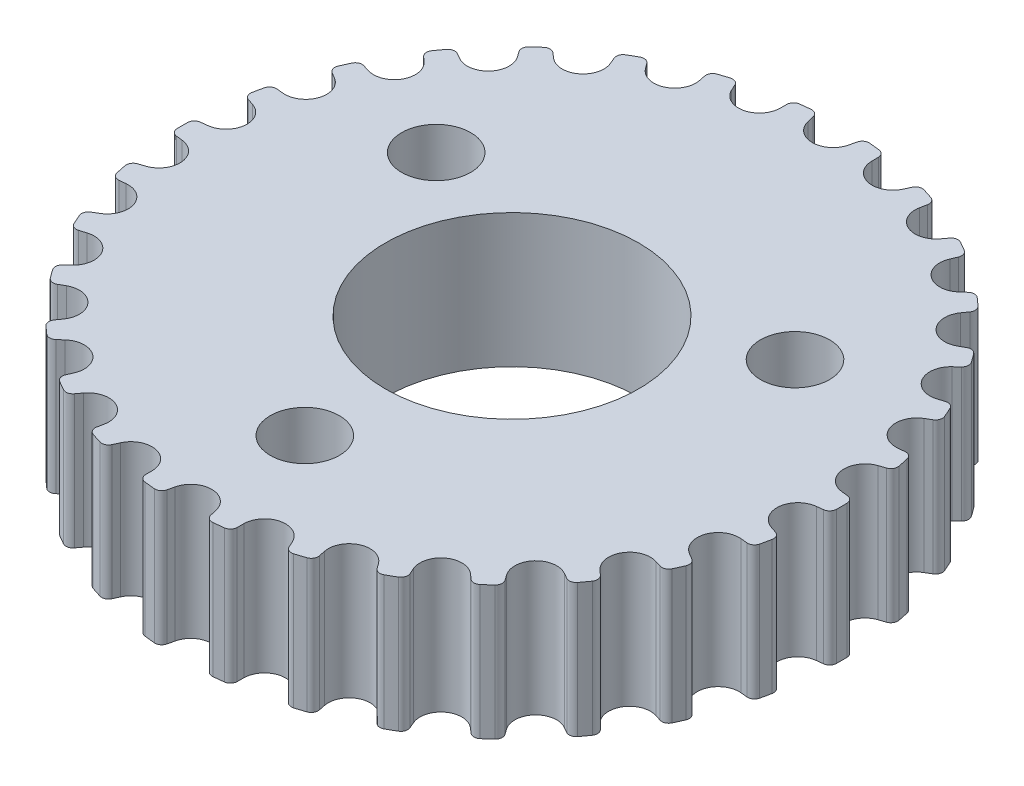
SolidWorks part; units mm, degrees
material "Acrylic (Medium-high impact)"
ref_plane "Front Plane" through (0, 0, 0) normal (0, 0, 1) x (1, 0, 0)
ref_plane "Top Plane" through (0, 0, 0) normal (0, 1, 0) x (1, 0, 0)
ref_plane "Right Plane" through (0, 0, 0) normal (1, 0, 0) x (0, 0, -1)
sketch "Sketch1" plane through (0, 0, 0) normal (0, 1, 0) x (1, 0, 0)
  circle A0 centre (0, 0) radius 14.3239
  dimension "D1" = 28.6479
extrude "Boss-Extrude1" add sketch "Sketch1" along normal blind 5.8
sketch "Sketch2" plane through (0, 5.8, 0) normal (0, 1, 0) x (1, 0, 0)
  line L0 (0, 0) -> (0, 14.3239) construction
  line L1 (-0.8883, 13.7564) -> (-0.95, 14.0339)
  line L2 (-2.9781, 14.0109) -> (-2.9781, 14.3239)
  line L3 (-2.9781, 14.3239) -> (2.9781, 14.3239)
  line L4 (0.8883, 13.7564) -> (0.95, 14.0339)
  line L5 (2.9781, 14.0109) -> (2.9781, 14.3239)
  circle A0 centre (0, 0) radius 14.3239 construction
  arc A1 (0.8883, 13.7564) -> (-0.8883, 13.7564) centre (0, 13.9539) cw
  arc A2 (-0.95, 14.0339) -> (-1.2694, 14.2676) centre (-1.2428, 13.9688) ccw
  arc A4 (0.95, 14.0339) -> (1.2694, 14.2676) centre (1.2428, 13.9688) cw
  arc A5 (-1.2694, 14.2676) -> (-2.9781, 14.0109) centre (0, 0) ccw
  arc A6 (1.2694, 14.2676) -> (2.9781, 14.0109) centre (0, 0) cw
  circle A8 centre (0, 0) radius 14.3239 construction
  point P11 (0, 14.3239)
  point P19 (0, 13.0439)
  dimension "D3" = 0.3
  dimension "D5" = 0.91
  dimension "D2" = 0.95
  dimension "D4" = 1.28
  dimension "D6" = 12
extrude "Cut-Extrude1" cut sketch "Sketch2" against normal through all
pattern_circular "CirPattern1" count 30 over 360 about axis through (0, 5.8, 0) along (0, -1, 0) of "Cut-Extrude1"
sketch "Sketch3" plane through (0, 0, 0) normal (0, -1, 0) x (1, 0, 0)
  circle A0 centre (0, 0) radius 5.5
  dimension "D1" = 11
extrude "Cut-Extrude2" cut sketch "Sketch3" against normal through all
sketch "Sketch4" plane through (0, 0, 0) normal (0, -1, 0) x (1, 0, 0)
  line L0 (0, 0) -> (0, 9) construction
  circle A0 centre (0, 9) radius 1.5
  circle A1 centre (7.7942, -4.5) radius 1.5
  circle A2 centre (-7.7942, -4.5) radius 1.5
  point P14 (0, 0)
  dimension "D1" = 3
  dimension "D2" = 9
  dimension "D3" = 3
extrude "Cut-Extrude3" cut sketch "Sketch4" against normal through all
sketch "Sketch5" plane through (0, 0, 0) normal (0, -1, 0) x (1, 0, 0)
  line L60 (8.7383, -10.682) -> (8.9513, -10.8702)
  line L61 (8.7383, -10.682) -> (8.9513, -10.8702)
  line L62 (9.875, -10.0385) -> (9.7101, -9.807)
  line L63 (9.875, -10.0385) -> (9.7101, -9.807)
  line L64 (12.5987, 6.2896) -> (12.3276, 6.2043)
  line L65 (12.5987, 6.2896) -> (12.3276, 6.2043)
  line L66 (11.5369, 7.5738) -> (11.7463, 7.766)
  line L67 (11.5369, 7.5738) -> (11.7463, 7.766)
  line L68 (-3.638, 13.3126) -> (-3.7561, 13.5712)
  line L69 (-3.638, 13.3126) -> (-3.7561, 13.5712)
  line L70 (-4.9382, 13.1871) -> (-4.8817, 12.9085)
  line L71 (-4.9382, 13.1871) -> (-4.8817, 12.9085)
  line L72 (-11.7463, 7.766) -> (-11.5369, 7.5738)
  line L73 (-11.7463, 7.766) -> (-11.5369, 7.5738)
  line L74 (-12.3276, 6.2043) -> (-12.5987, 6.2896)
  line L75 (-12.3276, 6.2043) -> (-12.5987, 6.2896)
  line L76 (-13.1043, 5.1541) -> (-12.8594, 5.0097)
  line L77 (-13.1043, 5.1541) -> (-12.8594, 5.0097)
  line L78 (-13.3481, 3.5057) -> (-13.6311, 3.5327)
  line L79 (-13.3481, 3.5057) -> (-13.6311, 3.5327)
  line L80 (-13.8895, 2.3169) -> (-13.62, 2.2266)
  line L81 (-13.8895, 2.3169) -> (-13.62, 2.2266)
  line L82 (-13.7853, 0.6538) -> (-14.0677, 0.6215)
  line L83 (-13.7853, 0.6538) -> (-14.0677, 0.6215)
  line L84 (-14.0677, -0.6215) -> (-13.7853, -0.6538)
  line L85 (-14.0677, -0.6215) -> (-13.7853, -0.6538)
  line L86 (-13.62, -2.2266) -> (-13.8895, -2.3169)
  line L87 (-13.62, -2.2266) -> (-13.8895, -2.3169)
  line L88 (-13.6311, -3.5327) -> (-13.3481, -3.5057)
  line L89 (-13.6311, -3.5327) -> (-13.3481, -3.5057)
  line L90 (-12.8594, -5.0097) -> (-13.1043, -5.1541)
  line L91 (-12.8594, -5.0097) -> (-13.1043, -5.1541)
  line L92 (-12.5987, -6.2896) -> (-12.3276, -6.2043)
  line L93 (-12.5987, -6.2896) -> (-12.3276, -6.2043)
  line L94 (-11.5369, -7.5738) -> (-11.7463, -7.766)
  line L95 (-11.5369, -7.5738) -> (-11.7463, -7.766)
  line L96 (-11.0157, -8.7716) -> (-10.7682, -8.6318)
  line L97 (-11.0157, -8.7716) -> (-10.7682, -8.6318)
  line L98 (-9.7101, -9.807) -> (-9.875, -10.0385)
  line L99 (-9.7101, -9.807) -> (-9.875, -10.0385)
  line L100 (-8.9513, -10.8702) -> (-8.7383, -10.682)
  line L101 (-8.9513, -10.8702) -> (-8.7383, -10.682)
  line L102 (-7.4589, -11.6115) -> (-7.5721, -11.8722)
  line L103 (-7.4589, -11.6115) -> (-7.5721, -11.8722)
  line L104 (-6.4956, -12.4937) -> (-6.3264, -12.2653)
  line L105 (-6.4956, -12.4937) -> (-6.3264, -12.2653)
  line L106 (-4.8817, -12.9085) -> (-4.9382, -13.1871)
  line L107 (-4.8817, -12.9085) -> (-4.9382, -13.1871)
  line L108 (-3.7561, -13.5712) -> (-3.638, -13.3126)
  line L109 (-3.7561, -13.5712) -> (-3.638, -13.3126)
  line L110 (-2.0912, -13.6414) -> (-2.0886, -13.9257)
  line L111 (-2.0912, -13.6414) -> (-2.0886, -13.9257)
  line L120 (6.3264, -12.2653) -> (6.4956, -12.4937)
  line L121 (7.5721, -11.8722) -> (7.4589, -11.6115)
  line L124 (10.7682, -8.6318) -> (11.0157, -8.7716)
  line L125 (11.7463, -7.766) -> (11.5369, -7.5738)
  line L126 (12.3276, -6.2043) -> (12.5987, -6.2896)
  line L127 (13.1043, -5.1541) -> (12.8594, -5.0097)
  line L128 (13.3481, -3.5057) -> (13.6311, -3.5327)
  line L129 (13.8895, -2.3169) -> (13.62, -2.2266)
  line L130 (13.7853, -0.6538) -> (14.0677, -0.6215)
  line L131 (14.0677, 0.6215) -> (13.7853, 0.6538)
  line L132 (13.62, 2.2266) -> (13.8895, 2.3169)
  line L133 (13.6311, 3.5327) -> (13.3481, 3.5057)
  line L134 (12.8594, 5.0097) -> (13.1043, 5.1541)
  line L137 (11.0157, 8.7716) -> (10.7682, 8.6318)
  line L138 (9.7101, 9.807) -> (9.875, 10.0385)
  line L139 (8.9513, 10.8702) -> (8.7383, 10.682)
  line L140 (7.4589, 11.6115) -> (7.5721, 11.8722)
  line L141 (6.4956, 12.4937) -> (6.3264, 12.2653)
  line L142 (4.8817, 12.9085) -> (4.9382, 13.1871)
  line L143 (3.7561, 13.5712) -> (3.638, 13.3126)
  line L144 (2.0912, 13.6414) -> (2.0886, 13.9257)
  line L145 (0.8524, 14.0556) -> (0.7907, 13.7781)
  line L146 (-0.7907, 13.7781) -> (-0.8524, 14.0556)
  line L147 (-2.0886, 13.9257) -> (-2.0912, 13.6414)
  line L150 (-6.3264, 12.2653) -> (-6.4956, 12.4937)
  line L151 (-7.5721, 11.8722) -> (-7.4589, 11.6115)
  line L152 (-8.7383, 10.682) -> (-8.9513, 10.8702)
  line L153 (-9.875, 10.0385) -> (-9.7101, 9.807)
  line L154 (-10.7682, 8.6318) -> (-11.0157, 8.7716)
  line L175 (-0.8524, -14.0556) -> (-0.7907, -13.7781)
  line L176 (0.7907, -13.7781) -> (0.8524, -14.0556)
  line L177 (2.0886, -13.9257) -> (2.0912, -13.6414)
  line L178 (3.638, -13.3126) -> (3.7561, -13.5712)
  line L179 (4.9382, -13.1871) -> (4.8817, -12.9085)
  line L180 (6.3264, -12.2653) -> (6.4956, -12.4937)
  line L181 (7.5721, -11.8722) -> (7.4589, -11.6115)
  line L184 (10.7682, -8.6318) -> (11.0157, -8.7716)
  line L185 (11.7463, -7.766) -> (11.5369, -7.5738)
  line L186 (12.3276, -6.2043) -> (12.5987, -6.2896)
  line L187 (13.1043, -5.1541) -> (12.8594, -5.0097)
  line L188 (13.3481, -3.5057) -> (13.6311, -3.5327)
  line L189 (13.8895, -2.3169) -> (13.62, -2.2266)
  line L190 (13.7853, -0.6538) -> (14.0677, -0.6215)
  line L191 (14.0677, 0.6215) -> (13.7853, 0.6538)
  line L192 (13.62, 2.2266) -> (13.8895, 2.3169)
  line L193 (13.6311, 3.5327) -> (13.3481, 3.5057)
  line L194 (12.8594, 5.0097) -> (13.1043, 5.1541)
  line L197 (11.0157, 8.7716) -> (10.7682, 8.6318)
  line L198 (9.7101, 9.807) -> (9.875, 10.0385)
  line L199 (8.9513, 10.8702) -> (8.7383, 10.682)
  line L200 (7.4589, 11.6115) -> (7.5721, 11.8722)
  line L201 (6.4956, 12.4937) -> (6.3264, 12.2653)
  line L202 (4.8817, 12.9085) -> (4.9382, 13.1871)
  line L203 (3.7561, 13.5712) -> (3.638, 13.3126)
  line L204 (2.0912, 13.6414) -> (2.0886, 13.9257)
  line L205 (0.8524, 14.0556) -> (0.7907, 13.7781)
  line L206 (-0.7907, 13.7781) -> (-0.8524, 14.0556)
  line L207 (-2.0886, 13.9257) -> (-2.0912, 13.6414)
  line L210 (-6.3264, 12.2653) -> (-6.4956, 12.4937)
  line L211 (-7.5721, 11.8722) -> (-7.4589, 11.6115)
  line L212 (-8.7383, 10.682) -> (-8.9513, 10.8702)
  line L213 (-9.875, 10.0385) -> (-9.7101, 9.807)
  line L214 (-10.7682, 8.6318) -> (-11.0157, 8.7716)
  line L235 (-0.8524, -14.0556) -> (-0.7907, -13.7781)
  line L236 (0.7907, -13.7781) -> (0.8524, -14.0556)
  line L237 (2.0886, -13.9257) -> (2.0912, -13.6414)
  line L238 (3.638, -13.3126) -> (3.7561, -13.5712)
  line L239 (4.9382, -13.1871) -> (4.8817, -12.9085)
  arc A76 (8.9513, -10.8702) -> (9.479, -10.8719) centre (9.2161, -10.5704) ccw
  arc A77 (8.9513, -10.8702) -> (9.479, -10.8719) centre (9.2161, -10.5704) ccw
  arc A78 (9.479, -10.8719) -> (9.8216, -10.5635) centre (0, 0) ccw
  arc A79 (9.479, -10.8719) -> (9.8216, -10.5635) centre (0, 0) ccw
  arc A80 (9.8216, -10.5635) -> (9.875, -10.0385) centre (9.5492, -10.2705) ccw
  arc A81 (9.8216, -10.5635) -> (9.875, -10.0385) centre (9.5492, -10.2705) ccw
  circle A120 centre (0, 0) radius 13.0439
  arc A121 (-0.8883, 13.7564) -> (0.8883, 13.7564) centre (0, 13.9539) ccw construction
  arc A128 (11.5369, 7.5738) -> (12.3276, 6.2043) centre (12.0845, 6.977) ccw
  arc A129 (11.5369, 7.5738) -> (12.3276, 6.2043) centre (12.0845, 6.977) ccw
  arc A130 (-3.7561, 13.5712) -> (-4.2375, 13.7875) centre (-4.12, 13.4051) ccw
  arc A131 (-3.7561, 13.5712) -> (-4.2375, 13.7875) centre (-4.12, 13.4051) ccw
  arc A132 (-4.2375, 13.7875) -> (-4.6759, 13.645) centre (0, 0) ccw
  arc A133 (-4.2375, 13.7875) -> (-4.6759, 13.645) centre (0, 0) ccw
  arc A134 (-4.6759, 13.645) -> (-4.9382, 13.1871) centre (-4.5462, 13.2666) ccw
  arc A135 (-4.6759, 13.645) -> (-4.9382, 13.1871) centre (-4.5462, 13.2666) ccw
  arc A136 (-11.8032, 8.2906) -> (-11.7463, 7.766) centre (-11.4759, 8.0607) ccw
  arc A137 (-11.8032, 8.2906) -> (-11.7463, 7.766) centre (-11.4759, 8.0607) ccw
  arc A138 (-12.3276, 6.2043) -> (-11.5369, 7.5738) centre (-12.0845, 6.977) ccw
  arc A139 (-12.3276, 6.2043) -> (-11.5369, 7.5738) centre (-12.0845, 6.977) ccw
  arc A140 (-12.5987, 6.2896) -> (-13.0815, 6.0766) centre (-12.7187, 5.908) ccw
  arc A141 (-12.5987, 6.2896) -> (-13.0815, 6.0766) centre (-12.7187, 5.908) ccw
  arc A142 (-13.0815, 6.0766) -> (-13.269, 5.6554) centre (0, 0) ccw
  arc A143 (-13.0815, 6.0766) -> (-13.269, 5.6554) centre (0, 0) ccw
  arc A144 (-13.269, 5.6554) -> (-13.1043, 5.1541) centre (-12.901, 5.4986) ccw
  arc A145 (-13.269, 5.6554) -> (-13.1043, 5.1541) centre (-12.901, 5.4986) ccw
  arc A146 (-13.3481, 3.5057) -> (-12.8594, 5.0097) centre (-13.271, 4.312) ccw
  arc A147 (-13.3481, 3.5057) -> (-12.8594, 5.0097) centre (-13.271, 4.312) ccw
  arc A148 (-13.6311, 3.5327) -> (-14.059, 3.224) centre (-13.6691, 3.1346) ccw
  arc A149 (-13.6311, 3.5327) -> (-14.059, 3.224) centre (-13.6691, 3.1346) ccw
  arc A150 (-14.059, 3.224) -> (-14.1549, 2.7731) centre (0, 0) ccw
  arc A151 (-14.059, 3.224) -> (-14.1549, 2.7731) centre (0, 0) ccw
  arc A152 (-14.1549, 2.7731) -> (-13.8895, 2.3169) centre (-13.7623, 2.6962) ccw
  arc A153 (-14.1549, 2.7731) -> (-13.8895, 2.3169) centre (-13.7623, 2.6962) ccw
  arc A154 (-13.7853, 0.6538) -> (-13.62, 2.2266) centre (-13.8775, 1.4586) ccw
  arc A155 (-13.7853, 0.6538) -> (-13.62, 2.2266) centre (-13.8775, 1.4586) ccw
  arc A156 (-14.0677, 0.6215) -> (-14.4221, 0.2305) centre (-14.0222, 0.2241) ccw
  arc A157 (-14.0677, 0.6215) -> (-14.4221, 0.2305) centre (-14.0222, 0.2241) ccw
  arc A158 (-14.4221, 0.2305) -> (-14.4221, -0.2305) centre (0, 0) ccw
  arc A159 (-14.4221, 0.2305) -> (-14.4221, -0.2305) centre (0, 0) ccw
  arc A160 (-14.4221, -0.2305) -> (-14.0677, -0.6215) centre (-14.0222, -0.2241) ccw
  arc A161 (-14.4221, -0.2305) -> (-14.0677, -0.6215) centre (-14.0222, -0.2241) ccw
  arc A162 (-13.62, -2.2266) -> (-13.7853, -0.6538) centre (-13.8775, -1.4586) ccw
  arc A163 (-13.62, -2.2266) -> (-13.7853, -0.6538) centre (-13.8775, -1.4586) ccw
  arc A164 (-13.8895, -2.3169) -> (-14.1549, -2.7731) centre (-13.7623, -2.6962) ccw
  arc A165 (-13.8895, -2.3169) -> (-14.1549, -2.7731) centre (-13.7623, -2.6962) ccw
  arc A166 (-14.1549, -2.7731) -> (-14.059, -3.224) centre (0, 0) ccw
  arc A167 (-14.1549, -2.7731) -> (-14.059, -3.224) centre (0, 0) ccw
  arc A168 (-14.059, -3.224) -> (-13.6311, -3.5327) centre (-13.6691, -3.1346) ccw
  arc A169 (-14.059, -3.224) -> (-13.6311, -3.5327) centre (-13.6691, -3.1346) ccw
  arc A170 (-12.8594, -5.0097) -> (-13.3481, -3.5057) centre (-13.271, -4.312) ccw
  arc A171 (-12.8594, -5.0097) -> (-13.3481, -3.5057) centre (-13.271, -4.312) ccw
  arc A172 (-13.1043, -5.1541) -> (-13.269, -5.6554) centre (-12.901, -5.4986) ccw
  arc A173 (-13.1043, -5.1541) -> (-13.269, -5.6554) centre (-12.901, -5.4986) ccw
  arc A174 (-13.269, -5.6554) -> (-13.0815, -6.0766) centre (0, 0) ccw
  arc A175 (-13.269, -5.6554) -> (-13.0815, -6.0766) centre (0, 0) ccw
  arc A176 (-13.0815, -6.0766) -> (-12.5987, -6.2896) centre (-12.7187, -5.908) ccw
  arc A177 (-13.0815, -6.0766) -> (-12.5987, -6.2896) centre (-12.7187, -5.908) ccw
  arc A178 (-11.5369, -7.5738) -> (-12.3276, -6.2043) centre (-12.0845, -6.977) ccw
  arc A179 (-11.5369, -7.5738) -> (-12.3276, -6.2043) centre (-12.0845, -6.977) ccw
  arc A180 (-11.7463, -7.766) -> (-11.8032, -8.2906) centre (-11.4759, -8.0607) ccw
  arc A181 (-11.7463, -7.766) -> (-11.8032, -8.2906) centre (-11.4759, -8.0607) ccw
  arc A182 (-11.8032, -8.2906) -> (-11.5323, -8.6636) centre (0, 0) ccw
  arc A183 (-11.8032, -8.2906) -> (-11.5323, -8.6636) centre (0, 0) ccw
  arc A184 (-11.5323, -8.6636) -> (-11.0157, -8.7716) centre (-11.2124, -8.4233) ccw
  arc A185 (-11.5323, -8.6636) -> (-11.0157, -8.7716) centre (-11.2124, -8.4233) ccw
  arc A186 (-9.7101, -9.807) -> (-10.7682, -8.6318) centre (-10.3698, -9.337) ccw
  arc A187 (-9.7101, -9.807) -> (-10.7682, -8.6318) centre (-10.3698, -9.337) ccw
  arc A188 (-9.875, -10.0385) -> (-9.8216, -10.5635) centre (-9.5492, -10.2705) ccw
  arc A189 (-9.875, -10.0385) -> (-9.8216, -10.5635) centre (-9.5492, -10.2705) ccw
  arc A190 (-9.8216, -10.5635) -> (-9.479, -10.8719) centre (0, 0) ccw
  arc A191 (-9.8216, -10.5635) -> (-9.479, -10.8719) centre (0, 0) ccw
  arc A192 (-9.479, -10.8719) -> (-8.9513, -10.8702) centre (-9.2161, -10.5704) ccw
  arc A193 (-9.479, -10.8719) -> (-8.9513, -10.8702) centre (-9.2161, -10.5704) ccw
  arc A194 (-7.4589, -11.6115) -> (-8.7383, -10.682) centre (-8.2019, -11.289) ccw
  arc A195 (-7.4589, -11.6115) -> (-8.7383, -10.682) centre (-8.2019, -11.289) ccw
  arc A196 (-7.5721, -11.8722) -> (-7.4107, -12.3747) centre (-7.2051, -12.0315) ccw
  arc A197 (-7.5721, -11.8722) -> (-7.4107, -12.3747) centre (-7.2051, -12.0315) ccw
  arc A198 (-7.4107, -12.3747) -> (-7.0114, -12.6052) centre (0, 0) ccw
  arc A199 (-7.4107, -12.3747) -> (-7.0114, -12.6052) centre (0, 0) ccw
  arc A200 (-7.0114, -12.6052) -> (-6.4956, -12.4937) centre (-6.817, -12.2556) ccw
  arc A201 (-7.0114, -12.6052) -> (-6.4956, -12.4937) centre (-6.817, -12.2556) ccw
  arc A202 (-4.8817, -12.9085) -> (-6.3264, -12.2653) centre (-5.6756, -12.7476) ccw
  arc A203 (-4.8817, -12.9085) -> (-6.3264, -12.2653) centre (-5.6756, -12.7476) ccw
  arc A204 (-4.9382, -13.1871) -> (-4.6759, -13.645) centre (-4.5462, -13.2666) ccw
  arc A205 (-4.9382, -13.1871) -> (-4.6759, -13.645) centre (-4.5462, -13.2666) ccw
  arc A206 (-4.6759, -13.645) -> (-4.2375, -13.7875) centre (0, 0) ccw
  arc A207 (-4.6759, -13.645) -> (-4.2375, -13.7875) centre (0, 0) ccw
  arc A208 (-4.2375, -13.7875) -> (-3.7561, -13.5712) centre (-4.12, -13.4051) ccw
  arc A209 (-4.2375, -13.7875) -> (-3.7561, -13.5712) centre (-4.12, -13.4051) ccw
  arc A210 (-2.0912, -13.6414) -> (-3.638, -13.3126) centre (-2.9012, -13.649) ccw
  arc A211 (-2.0912, -13.6414) -> (-3.638, -13.3126) centre (-2.9012, -13.649) ccw
  arc A212 (-2.0886, -13.9257) -> (-1.7367, -14.319) centre (-1.6886, -13.9219) ccw
  arc A213 (-2.0886, -13.9257) -> (-1.7367, -14.319) centre (-1.6886, -13.9219) ccw
  arc A214 (-1.7367, -14.319) -> (-1.2783, -14.3672) centre (0, 0) ccw
  arc A215 (-1.7367, -14.319) -> (-1.2783, -14.3672) centre (0, 0) ccw
  arc A240 (6.4956, -12.4937) -> (7.0114, -12.6052) centre (6.817, -12.2556) ccw
  arc A241 (7.0114, -12.6052) -> (7.4107, -12.3747) centre (0, 0) ccw
  arc A242 (7.4107, -12.3747) -> (7.5721, -11.8722) centre (7.2051, -12.0315) ccw
  arc A243 (8.7383, -10.682) -> (7.4589, -11.6115) centre (8.2019, -11.289) ccw
  arc A247 (10.7682, -8.6318) -> (9.7101, -9.807) centre (10.3698, -9.337) ccw
  arc A248 (11.0157, -8.7716) -> (11.5323, -8.6636) centre (11.2124, -8.4233) ccw
  arc A249 (11.5323, -8.6636) -> (11.8032, -8.2906) centre (0, 0) ccw
  arc A250 (11.8032, -8.2906) -> (11.7463, -7.766) centre (11.4759, -8.0607) ccw
  arc A251 (12.3276, -6.2043) -> (11.5369, -7.5738) centre (12.0845, -6.977) ccw
  arc A252 (12.5987, -6.2896) -> (13.0815, -6.0766) centre (12.7187, -5.908) ccw
  arc A253 (13.0815, -6.0766) -> (13.269, -5.6554) centre (0, 0) ccw
  arc A254 (13.269, -5.6554) -> (13.1043, -5.1541) centre (12.901, -5.4986) ccw
  arc A255 (13.3481, -3.5057) -> (12.8594, -5.0097) centre (13.271, -4.312) ccw
  arc A256 (13.6311, -3.5327) -> (14.059, -3.224) centre (13.6691, -3.1346) ccw
  arc A257 (14.059, -3.224) -> (14.1549, -2.7731) centre (0, 0) ccw
  arc A258 (14.1549, -2.7731) -> (13.8895, -2.3169) centre (13.7623, -2.6962) ccw
  arc A259 (13.7853, -0.6538) -> (13.62, -2.2266) centre (13.8775, -1.4586) ccw
  arc A260 (14.0677, -0.6215) -> (14.4221, -0.2305) centre (14.0222, -0.2241) ccw
  arc A261 (14.4221, -0.2305) -> (14.4221, 0.2305) centre (0, 0) ccw
  arc A262 (14.4221, 0.2305) -> (14.0677, 0.6215) centre (14.0222, 0.2241) ccw
  arc A263 (13.62, 2.2266) -> (13.7853, 0.6538) centre (13.8775, 1.4586) ccw
  arc A264 (13.8895, 2.3169) -> (14.1549, 2.7731) centre (13.7623, 2.6962) ccw
  arc A265 (14.1549, 2.7731) -> (14.059, 3.224) centre (0, 0) ccw
  arc A266 (14.059, 3.224) -> (13.6311, 3.5327) centre (13.6691, 3.1346) ccw
  arc A267 (12.8594, 5.0097) -> (13.3481, 3.5057) centre (13.271, 4.312) ccw
  arc A268 (13.1043, 5.1541) -> (13.269, 5.6554) centre (12.901, 5.4986) ccw
  arc A269 (13.269, 5.6554) -> (13.0815, 6.0766) centre (0, 0) ccw
  arc A270 (13.0815, 6.0766) -> (12.5987, 6.2896) centre (12.7187, 5.908) ccw
  arc A272 (11.7463, 7.766) -> (11.8032, 8.2906) centre (11.4759, 8.0607) ccw
  arc A273 (11.8032, 8.2906) -> (11.5323, 8.6636) centre (0, 0) ccw
  arc A274 (11.5323, 8.6636) -> (11.0157, 8.7716) centre (11.2124, 8.4233) ccw
  arc A275 (9.7101, 9.807) -> (10.7682, 8.6318) centre (10.3698, 9.337) ccw
  arc A276 (9.875, 10.0385) -> (9.8216, 10.5635) centre (9.5492, 10.2705) ccw
  arc A277 (9.8216, 10.5635) -> (9.479, 10.8719) centre (0, 0) ccw
  arc A278 (9.479, 10.8719) -> (8.9513, 10.8702) centre (9.2161, 10.5704) ccw
  arc A279 (7.4589, 11.6115) -> (8.7383, 10.682) centre (8.2019, 11.289) ccw
  arc A280 (7.5721, 11.8722) -> (7.4107, 12.3747) centre (7.2051, 12.0315) ccw
  arc A281 (7.4107, 12.3747) -> (7.0114, 12.6052) centre (0, 0) ccw
  arc A282 (7.0114, 12.6052) -> (6.4956, 12.4937) centre (6.817, 12.2556) ccw
  arc A283 (4.8817, 12.9085) -> (6.3264, 12.2653) centre (5.6756, 12.7476) ccw
  arc A284 (4.9382, 13.1871) -> (4.6759, 13.645) centre (4.5462, 13.2666) ccw
  arc A285 (4.6759, 13.645) -> (4.2375, 13.7875) centre (0, 0) ccw
  arc A286 (4.2375, 13.7875) -> (3.7561, 13.5712) centre (4.12, 13.4051) ccw
  arc A287 (2.0912, 13.6414) -> (3.638, 13.3126) centre (2.9012, 13.649) ccw
  arc A288 (2.0886, 13.9257) -> (1.7367, 14.319) centre (1.6886, 13.9219) ccw
  arc A289 (1.7367, 14.319) -> (1.2783, 14.3672) centre (0, 0) ccw
  arc A290 (1.2783, 14.3672) -> (0.8524, 14.0556) centre (1.2428, 13.9688) ccw
  arc A291 (-0.7907, 13.7781) -> (0.7907, 13.7781) centre (0, 13.9539) ccw
  arc A292 (-0.8524, 14.0556) -> (-1.2783, 14.3672) centre (-1.2428, 13.9688) ccw
  arc A293 (-1.2783, 14.3672) -> (-1.7367, 14.319) centre (0, 0) ccw
  arc A294 (-1.7367, 14.319) -> (-2.0886, 13.9257) centre (-1.6886, 13.9219) ccw
  arc A295 (-3.638, 13.3126) -> (-2.0912, 13.6414) centre (-2.9012, 13.649) ccw
  arc A299 (-6.3264, 12.2653) -> (-4.8817, 12.9085) centre (-5.6756, 12.7476) ccw
  arc A300 (-6.4956, 12.4937) -> (-7.0114, 12.6052) centre (-6.817, 12.2556) ccw
  arc A301 (-7.0114, 12.6052) -> (-7.4107, 12.3747) centre (0, 0) ccw
  arc A302 (-7.4107, 12.3747) -> (-7.5721, 11.8722) centre (-7.2051, 12.0315) ccw
  arc A303 (-8.7383, 10.682) -> (-7.4589, 11.6115) centre (-8.2019, 11.289) ccw
  arc A304 (-8.9513, 10.8702) -> (-9.479, 10.8719) centre (-9.2161, 10.5704) ccw
  arc A305 (-9.479, 10.8719) -> (-9.8216, 10.5635) centre (0, 0) ccw
  arc A306 (-9.8216, 10.5635) -> (-9.875, 10.0385) centre (-9.5492, 10.2705) ccw
  arc A307 (-10.7682, 8.6318) -> (-9.7101, 9.807) centre (-10.3698, 9.337) ccw
  arc A308 (-11.0157, 8.7716) -> (-11.5323, 8.6636) centre (-11.2124, 8.4233) ccw
  arc A309 (-11.5323, 8.6636) -> (-11.8032, 8.2906) centre (0, 0) ccw
  arc A350 (-1.2783, -14.3672) -> (-0.8524, -14.0556) centre (-1.2428, -13.9688) ccw
  arc A351 (0.7907, -13.7781) -> (-0.7907, -13.7781) centre (0, -13.9539) ccw
  arc A352 (0.8524, -14.0556) -> (1.2783, -14.3672) centre (1.2428, -13.9688) ccw
  arc A353 (1.2783, -14.3672) -> (1.7367, -14.319) centre (0, 0) ccw
  arc A354 (1.7367, -14.319) -> (2.0886, -13.9257) centre (1.6886, -13.9219) ccw
  arc A355 (3.638, -13.3126) -> (2.0912, -13.6414) centre (2.9012, -13.649) ccw
  arc A356 (3.7561, -13.5712) -> (4.2375, -13.7875) centre (4.12, -13.4051) ccw
  arc A357 (4.2375, -13.7875) -> (4.6759, -13.645) centre (0, 0) ccw
  arc A358 (4.6759, -13.645) -> (4.9382, -13.1871) centre (4.5462, -13.2666) ccw
  arc A359 (6.3264, -12.2653) -> (4.8817, -12.9085) centre (5.6756, -12.7476) ccw
  arc A360 (6.4956, -12.4937) -> (7.0114, -12.6052) centre (6.817, -12.2556) ccw
  arc A361 (7.0114, -12.6052) -> (7.4107, -12.3747) centre (0, 0) ccw
  arc A362 (7.4107, -12.3747) -> (7.5721, -11.8722) centre (7.2051, -12.0315) ccw
  arc A363 (8.7383, -10.682) -> (7.4589, -11.6115) centre (8.2019, -11.289) ccw
  arc A367 (10.7682, -8.6318) -> (9.7101, -9.807) centre (10.3698, -9.337) ccw
  arc A368 (11.0157, -8.7716) -> (11.5323, -8.6636) centre (11.2124, -8.4233) ccw
  arc A369 (11.5323, -8.6636) -> (11.8032, -8.2906) centre (0, 0) ccw
  arc A370 (11.8032, -8.2906) -> (11.7463, -7.766) centre (11.4759, -8.0607) ccw
  arc A371 (12.3276, -6.2043) -> (11.5369, -7.5738) centre (12.0845, -6.977) ccw
  arc A372 (12.5987, -6.2896) -> (13.0815, -6.0766) centre (12.7187, -5.908) ccw
  arc A373 (13.0815, -6.0766) -> (13.269, -5.6554) centre (0, 0) ccw
  arc A374 (13.269, -5.6554) -> (13.1043, -5.1541) centre (12.901, -5.4986) ccw
  arc A375 (13.3481, -3.5057) -> (12.8594, -5.0097) centre (13.271, -4.312) ccw
  arc A376 (13.6311, -3.5327) -> (14.059, -3.224) centre (13.6691, -3.1346) ccw
  arc A377 (14.059, -3.224) -> (14.1549, -2.7731) centre (0, 0) ccw
  arc A378 (14.1549, -2.7731) -> (13.8895, -2.3169) centre (13.7623, -2.6962) ccw
  arc A379 (13.7853, -0.6538) -> (13.62, -2.2266) centre (13.8775, -1.4586) ccw
  arc A380 (14.0677, -0.6215) -> (14.4221, -0.2305) centre (14.0222, -0.2241) ccw
  arc A381 (14.4221, -0.2305) -> (14.4221, 0.2305) centre (0, 0) ccw
  arc A382 (14.4221, 0.2305) -> (14.0677, 0.6215) centre (14.0222, 0.2241) ccw
  arc A383 (13.62, 2.2266) -> (13.7853, 0.6538) centre (13.8775, 1.4586) ccw
  arc A384 (13.8895, 2.3169) -> (14.1549, 2.7731) centre (13.7623, 2.6962) ccw
  arc A385 (14.1549, 2.7731) -> (14.059, 3.224) centre (0, 0) ccw
  arc A386 (14.059, 3.224) -> (13.6311, 3.5327) centre (13.6691, 3.1346) ccw
  arc A387 (12.8594, 5.0097) -> (13.3481, 3.5057) centre (13.271, 4.312) ccw
  arc A388 (13.1043, 5.1541) -> (13.269, 5.6554) centre (12.901, 5.4986) ccw
  arc A389 (13.269, 5.6554) -> (13.0815, 6.0766) centre (0, 0) ccw
  arc A390 (13.0815, 6.0766) -> (12.5987, 6.2896) centre (12.7187, 5.908) ccw
  arc A392 (11.7463, 7.766) -> (11.8032, 8.2906) centre (11.4759, 8.0607) ccw
  arc A393 (11.8032, 8.2906) -> (11.5323, 8.6636) centre (0, 0) ccw
  arc A394 (11.5323, 8.6636) -> (11.0157, 8.7716) centre (11.2124, 8.4233) ccw
  arc A395 (9.7101, 9.807) -> (10.7682, 8.6318) centre (10.3698, 9.337) ccw
  arc A396 (9.875, 10.0385) -> (9.8216, 10.5635) centre (9.5492, 10.2705) ccw
  arc A397 (9.8216, 10.5635) -> (9.479, 10.8719) centre (0, 0) ccw
  arc A398 (9.479, 10.8719) -> (8.9513, 10.8702) centre (9.2161, 10.5704) ccw
  arc A399 (7.4589, 11.6115) -> (8.7383, 10.682) centre (8.2019, 11.289) ccw
  arc A400 (7.5721, 11.8722) -> (7.4107, 12.3747) centre (7.2051, 12.0315) ccw
  arc A401 (7.4107, 12.3747) -> (7.0114, 12.6052) centre (0, 0) ccw
  arc A402 (7.0114, 12.6052) -> (6.4956, 12.4937) centre (6.817, 12.2556) ccw
  arc A403 (4.8817, 12.9085) -> (6.3264, 12.2653) centre (5.6756, 12.7476) ccw
  arc A404 (4.9382, 13.1871) -> (4.6759, 13.645) centre (4.5462, 13.2666) ccw
  arc A405 (4.6759, 13.645) -> (4.2375, 13.7875) centre (0, 0) ccw
  arc A406 (4.2375, 13.7875) -> (3.7561, 13.5712) centre (4.12, 13.4051) ccw
  arc A407 (2.0912, 13.6414) -> (3.638, 13.3126) centre (2.9012, 13.649) ccw
  arc A408 (2.0886, 13.9257) -> (1.7367, 14.319) centre (1.6886, 13.9219) ccw
  arc A409 (1.7367, 14.319) -> (1.2783, 14.3672) centre (0, 0) ccw
  arc A410 (1.2783, 14.3672) -> (0.8524, 14.0556) centre (1.2428, 13.9688) ccw
  arc A411 (-0.7907, 13.7781) -> (0.7907, 13.7781) centre (0, 13.9539) ccw
  arc A412 (-0.8524, 14.0556) -> (-1.2783, 14.3672) centre (-1.2428, 13.9688) ccw
  arc A413 (-1.2783, 14.3672) -> (-1.7367, 14.319) centre (0, 0) ccw
  arc A414 (-1.7367, 14.319) -> (-2.0886, 13.9257) centre (-1.6886, 13.9219) ccw
  arc A415 (-3.638, 13.3126) -> (-2.0912, 13.6414) centre (-2.9012, 13.649) ccw
  arc A419 (-6.3264, 12.2653) -> (-4.8817, 12.9085) centre (-5.6756, 12.7476) ccw
  arc A420 (-6.4956, 12.4937) -> (-7.0114, 12.6052) centre (-6.817, 12.2556) ccw
  arc A421 (-7.0114, 12.6052) -> (-7.4107, 12.3747) centre (0, 0) ccw
  arc A422 (-7.4107, 12.3747) -> (-7.5721, 11.8722) centre (-7.2051, 12.0315) ccw
  arc A423 (-8.7383, 10.682) -> (-7.4589, 11.6115) centre (-8.2019, 11.289) ccw
  arc A424 (-8.9513, 10.8702) -> (-9.479, 10.8719) centre (-9.2161, 10.5704) ccw
  arc A425 (-9.479, 10.8719) -> (-9.8216, 10.5635) centre (0, 0) ccw
  arc A426 (-9.8216, 10.5635) -> (-9.875, 10.0385) centre (-9.5492, 10.2705) ccw
  arc A427 (-10.7682, 8.6318) -> (-9.7101, 9.807) centre (-10.3698, 9.337) ccw
  arc A428 (-11.0157, 8.7716) -> (-11.5323, 8.6636) centre (-11.2124, 8.4233) ccw
  arc A429 (-11.5323, 8.6636) -> (-11.8032, 8.2906) centre (0, 0) ccw
  arc A470 (-1.2783, -14.3672) -> (-0.8524, -14.0556) centre (-1.2428, -13.9688) ccw
  arc A471 (0.7907, -13.7781) -> (-0.7907, -13.7781) centre (0, -13.9539) ccw
  arc A472 (0.8524, -14.0556) -> (1.2783, -14.3672) centre (1.2428, -13.9688) ccw
  arc A473 (1.2783, -14.3672) -> (1.7367, -14.319) centre (0, 0) ccw
  arc A474 (1.7367, -14.319) -> (2.0886, -13.9257) centre (1.6886, -13.9219) ccw
  arc A475 (3.638, -13.3126) -> (2.0912, -13.6414) centre (2.9012, -13.649) ccw
  arc A476 (3.7561, -13.5712) -> (4.2375, -13.7875) centre (4.12, -13.4051) ccw
  arc A477 (4.2375, -13.7875) -> (4.6759, -13.645) centre (0, 0) ccw
  arc A478 (4.6759, -13.645) -> (4.9382, -13.1871) centre (4.5462, -13.2666) ccw
  arc A479 (6.3264, -12.2653) -> (4.8817, -12.9085) centre (5.6756, -12.7476) ccw
  dimension "D1" = 0.1
extrude "Boss-Extrude2" [suppressed] add sketch "Sketch5" against normal up to surface (5.8 mm away) up to face at (7.7942, 5.8, -6)
equation "\"smallPulleyTeeth\"= 15"
equation "\"largePulleyTeeth\"= 30"
equation "\"eighthThick\"= 2.9mm"
equation "\"D1@Sketch1\"=3*\"largePulleyTeeth\"/pi"
equation "\"D1@Boss-Extrude1\" = \"eighthThick\" * 2"
equation "\"D6@Sketch2\"=360/\"largePulleyTeeth\""
equation "\"quarterThick\"=6.0mm"
equation "\"D1@CirPattern1\"=\"largePulleyTeeth\""
equation "\"sixteenthThick\"= 1.7mm"
equation "\"OD\"= 145mm"
equation "\"puckAngle\"= 60.5deg"
equation "\"puckDiam\"= 76.5mm"
equation "\"axlePress\"= 5.9mm"
equation "\"press\"= 0.2mm"
equation "\"wheelClear\"= 0.3mm"
equation "\"10-32clear\"= 4.8mm"
equation "\"D1@Sketch4\"=\"4-40clear\""
equation "\"6-32clear\"= 3.3mm"
equation "\"8-32clear\"= 4.0mm"
equation "\"4-40clear\"= 3.0mm"
equation "\"wheelHeight\"= 22mm"
equation "\"wheelWell\"= 65mm"
